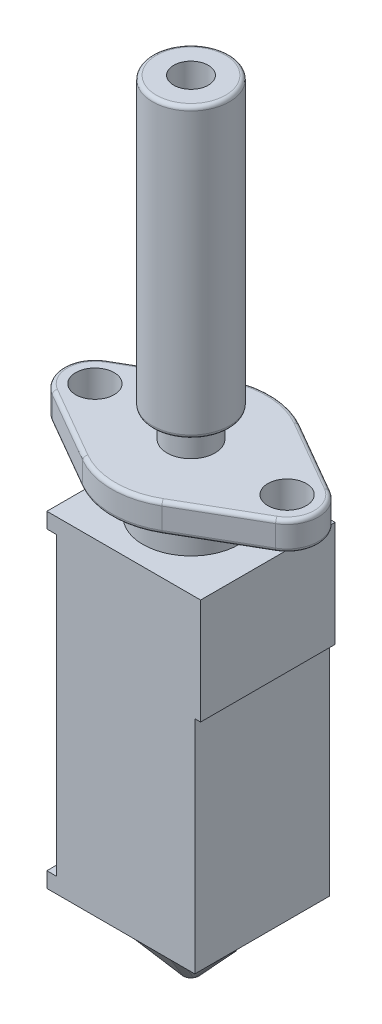
SolidWorks part; units mm, degrees
ref_plane "Front Plane" through (0, 0, 0) normal (0, 0, 1) x (1, 0, 0)
ref_plane "Top Plane" through (0, 0, 0) normal (0, 1, 0) x (1, 0, 0)
ref_plane "Right Plane" through (0, 0, 0) normal (1, 0, 0) x (0, 0, -1)
sketch "Sketch1" plane through (0, 0, 0) normal (0, 1, 0) x (1, 0, 0)
  line L1 (-4, 3.5) -> (4, 3.5)
  line L2 (-4, 3.5) -> (-4, -3.5)
  line L3 (-4, -3.5) -> (4, -3.5)
  line L4 (4, 3.5) -> (4, -3.5)
  line L5 (-4, 3.5) -> (4, -3.5) construction
  line L6 (-4, -3.5) -> (4, 3.5) construction
  point P0 (0, 0)
  dimension "D1" = 7
  dimension "D2" = 8
extrude "Boss-Extrude1" add sketch "Sketch1" along normal blind 17
sketch "Sketch2" plane through (0, 0, 0) normal (0, -1, 0) x (-1, 0, 0)
  line L1 (-2.3094, 0) -> (-1.1547, -2)
  line L2 (-1.1547, -2) -> (1.1547, -2)
  line L3 (1.1547, -2) -> (2.3094, 0)
  line L4 (2.3094, 0) -> (1.1547, 2)
  line L5 (1.1547, 2) -> (-1.1547, 2)
  line L6 (-1.1547, 2) -> (-2.3094, 0)
  circle A0 centre (0, 0) radius 2 construction
  dimension "D1" = 4
extrude "Boss-Extrude2" add sketch "Sketch2" along normal blind 4
chamfer "Chamfer1" distance 2.5 distance2 2 6 edges at (0, -4, 2) (1.7321, -4, 1) (1.7321, -4, -1) (0, -4, -2) (-1.7321, -4, -1) (-1.7321, -4, 1) first distance on face at (0, -2, 2) first distance on face at (1.7321, -2, 1) first distance on face at (1.7321, -2, -1) first distance on face at (0, -2, -2) first distance on face at (-1.7321, -2, -1) first distance on face at (-1.7321, -2, 1)
sketch "Sketch3" plane through (0, 0, 0) normal (0, -1, 0) x (-1, 0, 0)
  circle A0 centre (0, 0) radius 0.4
extrude "Cut-Extrude1" cut sketch "Sketch3" along normal through all
fillet "Fillet2" radius 0.5 6 edges at (0.6774, -2.5335, -1.1732) (-0.6774, -2.5335, -1.1732) (1.3547, -2.5335, 0) (0.6774, -2.5335, 1.1732) (-0.6774, -2.5335, 1.1732) (-1.3547, -2.5335, 0)
sketch "Sketch4" plane through (0, 0, 3.5) normal (0, 0, 1) x (1, 0, 0)
  line L0 (-4, 17) -> (-4, 0) construction
  line L1 (-4, 16.2) -> (-3.5, 16.2)
  line L2 (-4, 16.2) -> (-4, 0.8)
  line L3 (-4, 0.8) -> (-3.5, 0.8)
  line L4 (-3.5, 16.2) -> (-3.5, 0.8)
  dimension "D1" = 0.8
  dimension "D2" = 0.5
  dimension "D3" = 0.8
extrude "Cut-Extrude2" cut sketch "Sketch4" against normal through all
sketch "Sketch5" plane through (0, 0, 3.5) normal (0, 0, 1) x (1, 0, 0)
  line L0 (4, 17) -> (4, 0) construction
  line L1 (4, 11.5) -> (3.7, 11.5)
  line L2 (4, 11.5) -> (4, 0)
  line L3 (4, 0) -> (3.7, 0)
  line L4 (3.7, 11.5) -> (3.7, 0)
  line L5 (-4, 0) -> (4, 0) construction
  dimension "D1" = 0.3
  dimension "D2" = 11.5
extrude "Cut-Extrude3" cut sketch "Sketch5" against normal through all
sketch "Sketch6" plane through (0, 17, 0) normal (0, 1, 0) x (1, 0, 0)
  circle A0 centre (0, 0) radius 0.9
  dimension "D1" = 1.8
extrude "Cut-Extrude4" cut sketch "Sketch6" against normal blind 18
chamfer "Chamfer2" distance 0.5 angle 45 1 edges at (0, -1, 0.9)
sketch "Sketch7" plane through (0, 17, 0) normal (0, 1, 0) x (1, 0, 0)
  circle A0 centre (0, 0) radius 0.9
  circle A1 centre (0, 0) radius 2.5
  dimension "D1" = 5
extrude "Boss-Extrude3" add sketch "Sketch7" along normal blind 2
sketch "Sketch8" plane through (0, 19, 0) normal (0, 1, 0) x (1, 0, 0)
  line L0 (2.0625, 3.5724) -> (5.8125, 1.4073)
  line L1 (5.8125, -1.4073) -> (2.0625, -3.5724)
  line L2 (-2.0625, 3.5724) -> (-5.8125, 1.4073)
  line L3 (-5.8125, -1.4073) -> (-2.0625, -3.5724)
  arc A0 (2.0625, 3.5724) -> (-2.0625, 3.5724) centre (0, 0) ccw
  circle A1 centre (0, 0) radius 0.9
  arc A2 (5.8125, -1.4073) -> (5.8125, 1.4073) centre (5, 0) ccw
  arc A3 (-5.8125, 1.4073) -> (-5.8125, -1.4073) centre (-5, 0) ccw
  arc A4 (-2.0625, -3.5724) -> (2.0625, -3.5724) centre (0, 0) ccw
  circle A5 centre (5, 0) radius 1
  circle A6 centre (-5, 0) radius 1
  point P7 (-4.9565, 0)
  dimension "D1" = 8.25
  dimension "D2" = 3.25
  dimension "D3" = 2
  dimension "D4" = 10
  dimension "D6" = 1.8
  dimension "D5" = 5
extrude "Boss-Extrude4" add sketch "Sketch8" along normal blind 1.5
sketch "Sketch9" plane through (0, 20.5, 0) normal (0, 1, 0) x (1, 0, 0)
  circle A0 centre (0, 0) radius 0.9
  circle A1 centre (0, 0) radius 1.25
  dimension "D1" = 2.5
  dimension "D2" = 1.8
extrude "Boss-Extrude5" add sketch "Sketch9" along normal blind 1.4
sketch "Sketch10" plane through (0, 21.9, 0) normal (0, 1, 0) x (1, 0, 0)
  circle A0 centre (0, 0) radius 0.9
  circle A1 centre (0, 0) radius 2
  dimension "D1" = 4
  dimension "D2" = 1.8
extrude "Boss-Extrude6" add sketch "Sketch10" along normal blind 15
fillet "Fillet3" radius 0.2 18 edges at (-6.625, 19, 0) (-3.9375, 19, -2.4898) (0, 19, -4.125) (3.9375, 19, -2.4898) (6.625, 19, 0) (3.9375, 19, 2.4898) (0, 19, 4.125) (0, 20.5, -4.125) (3.9375, 20.5, -2.4898) (6.625, 20.5, 0) (3.9375, 20.5, 2.4898) (0, 20.5, 4.125) (-3.9375, 20.5, 2.4898) (-6.625, 20.5, 0) (-3.9375, 19, 2.4898) (-3.9375, 20.5, -2.4898) (0, 21.9, 2) (0, 36.9, 2)
